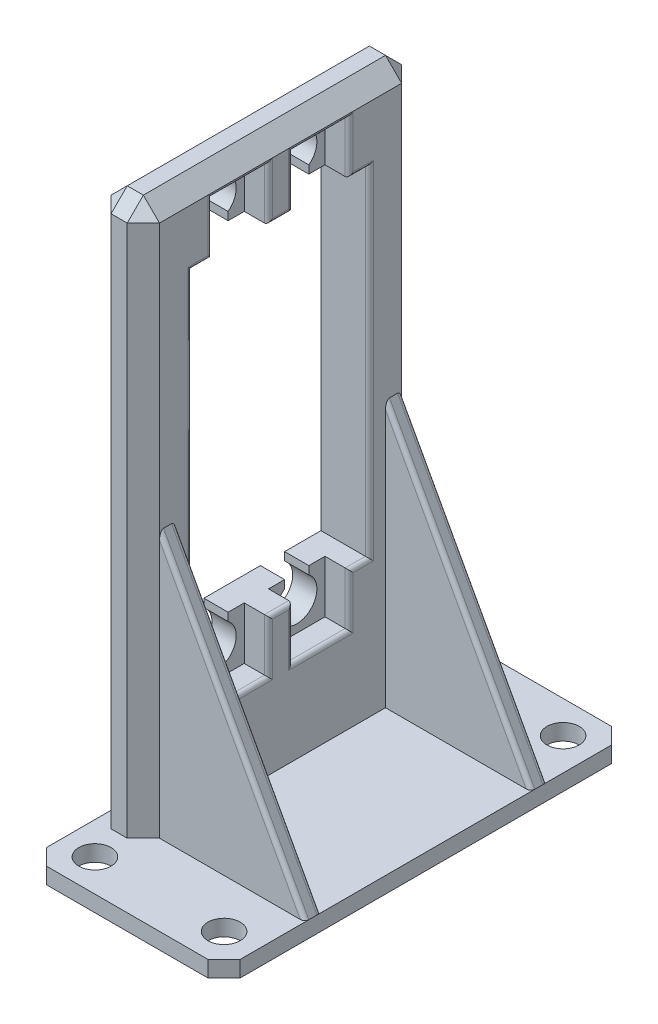
SolidWorks part; units mm, degrees
ref_plane "Front Plane" through (0, 0, 0) normal (0, 0, 1) x (1, 0, 0)
ref_plane "Top Plane" through (0, 0, 0) normal (0, 1, 0) x (1, 0, 0)
ref_plane "Right Plane" through (0, 0, 0) normal (1, 0, 0) x (0, 0, -1)
sketch "Sketch1" plane through (0, 0, 0) normal (1, 0, 0) x (0, 0, -1)
  line L0 (-17, -40) -> (-17, 30)
  line L1 (-11, -21) -> (11, -21)
  line L2 (-11, -21) -> (-11, 21)
  line L3 (-11, 21) -> (11, 21)
  line L4 (11, -21) -> (11, 21)
  line L5 (-11, -21) -> (11, 21) construction
  line L6 (-11, 21) -> (11, -21) construction
  line L7 (-17, 30) -> (17, 30)
  line L8 (17, 30) -> (17, -40)
  line L9 (0, 0) -> (0, 50000) construction
  line L10 (-17, -40) -> (17, -40)
  line L11 (23, -40) -> (-23, -40) construction
  point P0 (0, 0)
  dimension "D1" = 42
  dimension "D2" = 22
  dimension "D3" = 6
  dimension "D4" = 9
extrude "Boss-Extrude1" add sketch "Sketch1" along normal mid plane 6 contours L1 L4 L3 L2 | L8 L10 L0 L7 region at (0, 0, 0)
sketch "Sketch2" plane through (-3, 0, 0) normal (-1, 0, 0) x (0, 0, 1)
  line L0 (-6.5, -21) -> (-6.5, -22)
  line L1 (11, -21) -> (-11, -21) construction
  line L2 (-3.5, -21) -> (-3.5, -22)
  line L3 (-5, -21.5) -> (-5, -21) construction
  line L4 (5, -24) -> (-5, -24) construction
  line L5 (-5, 24) -> (5, 24) construction
  line L6 (0, 24) -> (0, -24) construction
  line L7 (-5, 0) -> (5, 0) construction
  line L8 (3.5, -21) -> (3.5, -22)
  line L9 (5, -21.5) -> (5, -21) construction
  line L10 (6.5, -21) -> (6.5, -22)
  line L11 (6.5, 21) -> (6.5, 22)
  line L12 (5, 21.5) -> (5, 21) construction
  line L13 (3.5, 21) -> (3.5, 22)
  line L14 (-3.5, 21) -> (-3.5, 22)
  line L15 (-5, 21.5) -> (-5, 21) construction
  line L16 (-6.5, 21) -> (-6.5, 22)
  line L17 (-6.5, 21) -> (-3.5, 21)
  line L18 (3.5, 21) -> (6.5, 21)
  line L19 (3.5, -21) -> (6.5, -21)
  line L20 (-3.5, -21) -> (-6.5, -21)
  arc A0 (-6.5, -22) -> (-3.5, -22) centre (-5, -24) ccw
  arc A1 (3.5, -22) -> (6.5, -22) centre (5, -24) ccw
  arc A2 (-3.5, 22) -> (-6.5, 22) centre (-5, 24) ccw
  arc A3 (6.5, 22) -> (3.5, 22) centre (5, 24) ccw
  arc A4 (3.375, 25.8998) -> (6.625, 25.8998) centre (5, 24) ccw construction
  arc A5 (-6.625, 25.8998) -> (-3.375, 25.8998) centre (-5, 24) ccw construction
  arc A6 (6.625, -25.8998) -> (3.375, -25.8998) centre (5, -24) ccw construction
  arc A7 (-3.375, -25.8998) -> (-6.625, -25.8998) centre (-5, -24) ccw construction
  dimension "D1" = 1
extrude "Cut-Extrude1" cut sketch "Sketch2" against normal through all
chamfer "Chamfer1" distance 2 angle 45 8 edges at (-3, -5, 17) (3, -5, 17) (0, 30, 17) (3, 30, 0) (-3, 30, 0) (-3, -5, -17) (0, 30, -17) (3, -5, -17)
sketch "Sketch3" plane through (3, 0, 0) normal (1, 0, 0) x (0, 0, -1)
  line L0 (0, 21) -> (0, -21) construction
  line L1 (-3.5, 21) -> (3.5, 21) construction
  line L2 (-3.5, -21) -> (3.5, -21) construction
  line L3 (11, 0) -> (-11, 0) construction
  line L4 (11, -21) -> (11, 21) construction
  line L5 (-11, -21) -> (-11, 21) construction
  line L6 (1.5, -20.5) -> (8.5, -27.5) construction
  line L7 (1.5, 27.5) -> (8.5, 27.5)
  line L8 (1.5, 27.5) -> (1.5, 20.5)
  line L9 (1.5, 20.5) -> (8.5, 20.5)
  line L10 (8.5, 27.5) -> (8.5, 20.5)
  line L11 (1.5, 27.5) -> (8.5, 20.5) construction
  line L12 (1.5, 20.5) -> (8.5, 27.5) construction
  line L13 (1.5, -27.5) -> (8.5, -20.5) construction
  line L14 (8.5, -27.5) -> (8.5, -20.5)
  line L15 (1.5, -20.5) -> (8.5, -20.5)
  line L16 (1.5, -27.5) -> (1.5, -20.5)
  line L17 (1.5, -27.5) -> (8.5, -27.5)
  line L18 (-1.5, -27.5) -> (-8.5, -20.5) construction
  line L19 (-1.5, 20.5) -> (-8.5, 27.5) construction
  line L20 (-1.5, 27.5) -> (-8.5, 20.5) construction
  line L21 (-1.5, -20.5) -> (-8.5, -27.5) construction
  line L22 (-1.5, -27.5) -> (-8.5, -27.5)
  line L23 (-1.5, -27.5) -> (-1.5, -20.5)
  line L24 (-1.5, -20.5) -> (-8.5, -20.5)
  line L25 (-8.5, -27.5) -> (-8.5, -20.5)
  line L26 (-8.5, 27.5) -> (-8.5, 20.5)
  line L27 (-1.5, 20.5) -> (-8.5, 20.5)
  line L28 (-1.5, 27.5) -> (-1.5, 20.5)
  line L29 (-1.5, 27.5) -> (-8.5, 27.5)
  point P12 (5, 24)
  point P22 (5, -24)
  point P31 (-5, -24)
  point P32 (-5, 24)
  dimension "D1" = 7
extrude "Cut-Extrude2" cut sketch "Sketch3" against normal blind 3
sketch "Sketch4" plane through (0, -40, 0) normal (0, -1, 0) x (1, 0, 0)
  line L0 (-3, 25) -> (-3, -25)
  line L1 (-3, 15) -> (-3, -15) construction
  line L2 (-3, -25) -> (21, -25)
  line L3 (21, -25) -> (21, 25)
  line L4 (21, 0) -> (-3, 0) construction
  line L5 (1, -21) -> (-3, -21) construction
  line L6 (1, -21) -> (1, -25) construction
  line L7 (17, -21) -> (21, -21) construction
  line L8 (17, 21) -> (21, 21) construction
  line L9 (1, 21) -> (1, 25) construction
  line L10 (1, 21) -> (-3, 21) construction
  line L11 (-3, 25) -> (21, 25)
  circle A0 centre (1, -21) radius 2
  circle A1 centre (17, -21) radius 2
  circle A2 centre (17, 21) radius 2
  circle A3 centre (1, 21) radius 2
  dimension "D3" = 4
  dimension "D1" = 25
  dimension "D2" = 4
  dimension "D4" = 16
extrude "Boss-Extrude2" add sketch "Sketch4" against normal blind 2 contours A1 | A0 | A3 | A2 | L2 L3 L11 L0 region at (1, -40, -21) region at (17, -40, -21) region at (17, -40, 21) region at (1, -40, 21)
chamfer "Chamfer2" distance 2 angle 45 4 edges at (21, -39, 25) (-3, -39, 25) (-3, -39, -25) (21, -39, -25)
sketch "Sketch5" plane through (0, 0, -25) normal (0, 0, -1) x (-1, 0, 0)
  line L0 (-3, -38) -> (-21, -38)
  line L1 (-21, -38) -> (-3, -5)
  line L2 (-3, -38) -> (-3, 28) construction
  line L3 (-3, -5) -> (-3, -38)
extrude "Boss-Extrude3" add sketch "Sketch5" against normal blind 2 from vertex starting at point (3, -38, -15)
extrude "Boss-Extrude4" add sketch "Sketch5<2>" along normal blind 2 from vertex contours L1 L3 L0 starting at point (3, -38, 15)
sketch "Sketch5<2>" plane through (0, 0, -25) normal (0, 0, -1) x (-1, 0, 0) same geometry as "Sketch5"
fillet "Fillet1" radius 0.5 24 edges at (3, -21, -9.75) (3, -24.25, -8.5) (3, -27.5, 5) (3, -21, 0) (3, -24.25, -1.5) (3, -27.5, -5) (3, -24.25, 1.5) (3, -24.25, 8.5) (3, -21, 9.75) (3, 21, 9.75) (3, 24.25, 8.5) (3, 27.5, 5) (3, 24.25, 1.5) (3, 21, 0) (3, 24.25, -1.5) (3, 27.5, -5) (3, 24.25, -8.5) (3, 21, -9.75) (3, 0, -11) (3, 0, 11) (12, -21.5, -15) (12, -21.5, -13) (12, -21.5, 13) (12, -21.5, 15)
